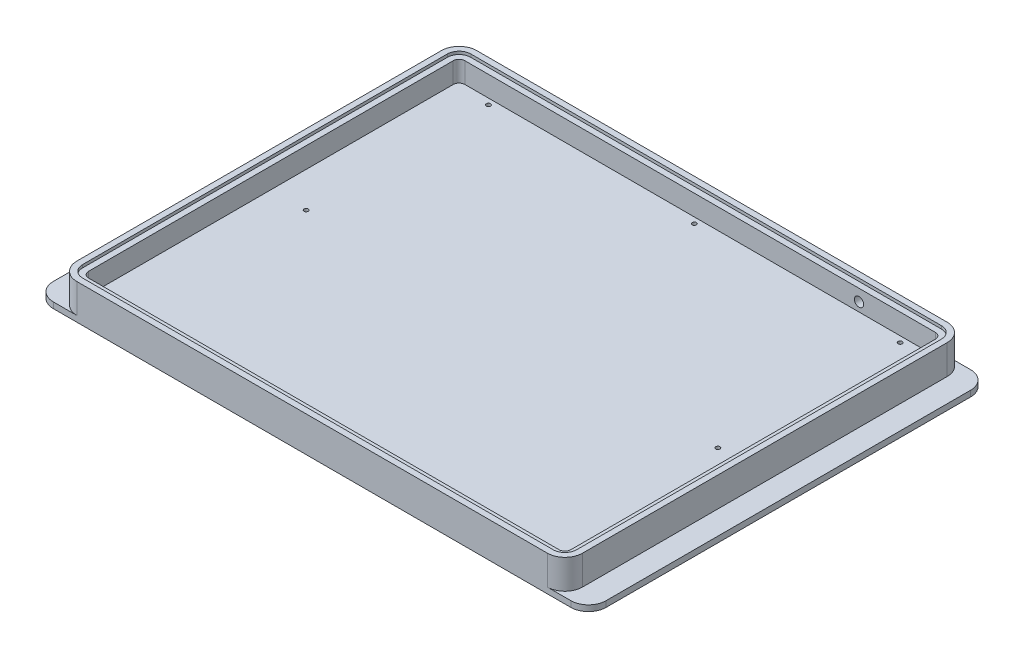
SolidWorks part; units mm, degrees
ref_plane "Front Plane" through (0, 0, 0) normal (0, 0, 1) x (1, 0, 0)
ref_plane "Top Plane" through (0, 0, 0) normal (0, 1, 0) x (1, 0, 0)
ref_plane "Right Plane" through (0, 0, 0) normal (1, 0, 0) x (0, 0, -1)
sketch "Sketch1" plane through (0, 0, 0) normal (0, 1, 0) x (1, 0, 0)
  line L1 (0, 0) -> (273.05, 0)
  line L2 (0, 0) -> (0, 215.9)
  line L3 (0, 215.9) -> (273.05, 215.9)
  line L4 (273.05, 0) -> (273.05, 215.9)
  dimension "D1" = 273.05
  dimension "D2" = 215.9
extrude "Boss-Extrude1" add sketch "Sketch1" along normal blind 19.05
fillet "Fillet1" radius 9.525 4 edges at (273.05, 9.525, 0) (273.05, 9.525, -215.9) (0, 9.525, 0) (0, 9.525, -215.9)
sketch "Sketch3" plane through (0, 19.05, 0) normal (0, 1, 0) x (1, 0, 0)
  line L25 (266.7, 9.525) -> (266.7, 206.375)
  line L26 (9.525, 6.35) -> (263.525, 6.35)
  line L27 (6.35, 206.375) -> (6.35, 9.525)
  line L28 (263.525, 209.55) -> (9.525, 209.55)
  line L29 (266.7, 9.525) -> (266.7, 206.375)
  line L30 (9.525, 6.35) -> (263.525, 6.35)
  line L31 (6.35, 206.375) -> (6.35, 9.525)
  line L32 (263.525, 209.55) -> (9.525, 209.55)
  arc A21 (266.7, 206.375) -> (263.525, 209.55) centre (263.525, 206.375) ccw
  arc A22 (263.525, 6.35) -> (266.7, 9.525) centre (263.525, 9.525) ccw
  arc A23 (6.35, 9.525) -> (9.525, 6.35) centre (9.525, 9.525) ccw
  arc A24 (9.525, 209.55) -> (6.35, 206.375) centre (9.525, 206.375) ccw
  arc A25 (266.7, 206.375) -> (263.525, 209.55) centre (263.525, 206.375) ccw
  arc A26 (263.525, 6.35) -> (266.7, 9.525) centre (263.525, 9.525) ccw
  arc A27 (6.35, 9.525) -> (9.525, 6.35) centre (9.525, 9.525) ccw
  arc A28 (9.525, 209.55) -> (6.35, 206.375) centre (9.525, 206.375) ccw
  dimension "D1" = 6.35
extrude "Cut-Extrude1" cut sketch "Sketch3" against normal blind 12.7
sketch "Sketch4" plane through (0, 19.05, 0) normal (0, 1, 0) x (1, 0, 0)
  line L24 (269.875, 9.525) -> (269.875, 206.375)
  line L25 (9.525, 3.175) -> (263.525, 3.175)
  line L26 (3.175, 206.375) -> (3.175, 9.525)
  line L27 (263.525, 212.725) -> (9.525, 212.725)
  line L28 (269.875, 9.525) -> (269.875, 206.375)
  line L29 (9.525, 3.175) -> (263.525, 3.175)
  line L30 (3.175, 206.375) -> (3.175, 9.525)
  line L31 (263.525, 212.725) -> (9.525, 212.725)
  arc A20 (269.875, 206.375) -> (263.525, 212.725) centre (263.525, 206.375) ccw
  arc A21 (263.525, 3.175) -> (269.875, 9.525) centre (263.525, 9.525) ccw
  arc A22 (3.175, 9.525) -> (9.525, 3.175) centre (9.525, 9.525) ccw
  arc A23 (9.525, 212.725) -> (3.175, 206.375) centre (9.525, 206.375) ccw
  arc A24 (269.875, 206.375) -> (263.525, 212.725) centre (263.525, 206.375) ccw
  arc A25 (263.525, 3.175) -> (269.875, 9.525) centre (263.525, 9.525) ccw
  arc A26 (3.175, 9.525) -> (9.525, 3.175) centre (9.525, 9.525) ccw
  arc A27 (9.525, 212.725) -> (3.175, 206.375) centre (9.525, 206.375) ccw
  dimension "D1" = 3.175
extrude "Cut-Extrude2" cut sketch "Sketch4" against normal blind 1.5875
sketch "Sketch5" plane through (0, 6.35, 0) normal (0, 1, 0) x (1, 0, 0)
  line L0 (136.525, 206.375) -> (136.525, 209.55) construction
  line L1 (25.4, 206.375) -> (247.65, 206.375) construction
  line L2 (25.4, 206.375) -> (25.4, 9.525) construction
  line L3 (25.4, 9.525) -> (247.65, 9.525) construction
  line L4 (247.65, 206.375) -> (247.65, 9.525) construction
  line L5 (263.525, 209.55) -> (9.525, 209.55) construction
  line L6 (25.4, 107.95) -> (6.35, 107.95) construction
  line L7 (6.35, 206.375) -> (6.35, 9.525) construction
  line L8 (247.65, 107.95) -> (266.7, 107.95) construction
  line L9 (266.7, 9.525) -> (266.7, 206.375) construction
  line L10 (136.525, 9.525) -> (136.525, 6.35) construction
  line L11 (263.525, 6.35) -> (9.525, 6.35) construction
  circle A0 centre (25.4, 206.375) radius 1.1303
  circle A1 centre (136.525, 206.375) radius 1.1303
  circle A2 centre (247.65, 206.375) radius 1.1303
  circle A3 centre (247.65, 107.95) radius 1.1303
  circle A4 centre (25.4, 107.95) radius 1.1303
  circle A5 centre (25.4, 9.525) radius 1.1303
  circle A6 centre (136.525, 9.525) radius 1.1303
  circle A7 centre (247.65, 9.525) radius 1.1303
  dimension "D3" = 2.2606
  dimension "D1" = 196.85
  dimension "D2" = 222.25
extrude "Cut-Extrude3" cut sketch "Sketch5" against normal blind 4.7625
sketch "Sketch6" plane through (0, 0, -215.9) normal (0, 0, -1) x (-1, 0, 0)
  line L1 (-273.05, 0) -> (-273.05, 19.05) construction
  line L3 (-263.525, 19.05) -> (-9.525, 19.05) construction
  circle A0 centre (-222.25, 11.1125) radius 2.5
  dimension "D2" = 5
  dimension "D1" = 50.8
  dimension "D3" = 7.9375
extrude "Cut-Extrude4" cut sketch "Sketch6" against normal blind 12.7
sketch "Sketch7" plane through (0, 0, 0) normal (0, -1, 0) x (1, 0, 0)
  line L0 (263.525, -215.9) -> (9.525, -215.9) construction
  line L1 (-3.175, 0) -> (276.225, 0)
  line L2 (-12.7, -9.525) -> (-12.7, -206.375)
  line L3 (-3.175, -215.9) -> (276.225, -215.9)
  line L4 (285.75, -9.525) -> (285.75, -206.375)
  line L5 (9.525, 0) -> (263.525, 0) construction
  line L6 (0, -206.375) -> (0, -9.525) construction
  line L7 (273.05, -9.525) -> (273.05, -206.375) construction
  arc A0 (-12.7, -206.375) -> (-3.175, -215.9) centre (-3.175, -206.375) ccw
  arc A1 (276.225, -215.9) -> (285.75, -206.375) centre (276.225, -206.375) ccw
  arc A2 (276.225, 0) -> (285.75, -9.525) centre (276.225, -9.525) cw
  arc A3 (-3.175, 0) -> (-12.7, -9.525) centre (-3.175, -9.525) ccw
  dimension "D3" = 9.525
  dimension "D1" = 12.7
  dimension "D2" = 12.7
extrude "Boss-Extrude2" add sketch "Sketch7" against normal blind 3.175
